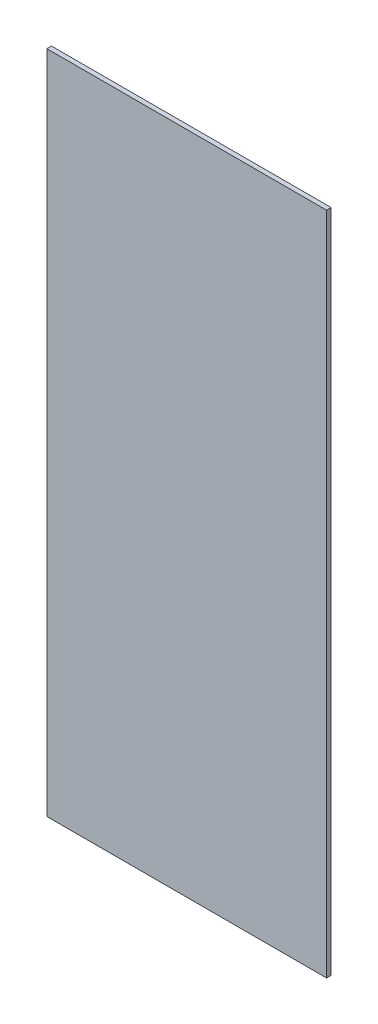
SolidWorks part; units mm, degrees
material "201 Annealed Stainless Steel (SS)"
ref_plane "Front Plane" through (0, 0, 0) normal (0, 0, 1) x (1, 0, 0)
ref_plane "Top Plane" through (0, 0, 0) normal (0, 1, 0) x (1, 0, 0)
ref_plane "Right Plane" through (0, 0, 0) normal (1, 0, 0) x (0, 0, -1)
sketch "Sketch1" plane through (0, 0, 0) normal (0, 0, 1) x (1, 0, 0)
  line L1 (-106, -145) -> (106, -145)
  line L2 (-106, -145) -> (-106, 145)
  line L3 (-106, 145) -> (106, 145)
  line L4 (106, -145) -> (106, 145)
  line L5 (-106, -145) -> (106, 145) construction
  line L6 (-106, 145) -> (106, -145) construction
  point P0 (0, 0)
  dimension "D1" = 212
  dimension "D2" = 290
extrude "Boss-Extrude1" add sketch "Sketch1" along normal blind 2
sketch "Sketch2" plane through (0, 0, 0) normal (0, 0, -1) x (-1, 0, 0)
  line L0 (61, 145) -> (61, -145) construction
  line L1 (-61, 314.7216) -> (-204.3993, 314.7216)
  line L2 (-61, 314.7216) -> (-61, -251.9618)
  line L3 (-61, -251.9618) -> (-204.3993, -251.9618)
  line L4 (-204.3993, 314.7216) -> (-204.3993, -251.9618)
  line L6 (61, 279.3211) -> (244.4765, 279.3211)
  line L7 (61, 279.3211) -> (61, -295.1839)
  line L8 (61, -295.1839) -> (244.4765, -295.1839)
  line L9 (244.4765, 279.3211) -> (244.4765, -295.1839)
  line L10 (-61, -145) -> (-61, 145) construction
  dimension "D1" = 122
extrude "Cut-Extrude1" cut sketch "Sketch2" against normal through all
sketch "Sketch3" [suppressed] plane through (49, 0, 0) normal (1, 0, 0) x (0, 0, -1)
  circle A0 centre (-6.722, 55.3681) radius 5.3835
surface "Surface-Extrude1" [suppressed] sketch "Sketch3"
sketch "Sketch4" [suppressed] plane through (-49, 0, 0) normal (-1, 0, 0) x (0, 0, 1)
  line L1 (2, 80) -> (0, 80) construction
  line L2 (0, -80) -> (0, 80) construction
  point P0 (7.5, 76)
  dimension "D1" = 4
  dimension "D2" = 7.5
ref_axis "Axis1" [suppressed] through (-49, 76, 7.5) along (1, 0, 0)
sketch "Sketch5" [suppressed] plane through (0, 0, 0) normal (0, 0, -1) x (-1, 0, 0)
  line L0 (49, 80) -> (49, -80) construction
  line L1 (-49, 80) -> (49, 80)
  line L2 (-49, 80) -> (-49, 60.2594)
  line L3 (-49, 60.2594) -> (49, 60.2594)
  line L4 (49, 80) -> (49, 60.2594)
extrude "Cut-Extrude2" [suppressed] cut sketch "Sketch5" against normal blind 3
sketch "Sketch6" [suppressed] plane through (0, 0, 2) normal (0, 0, 1) x (1, 0, 0)
  line L0 (0, 0) -> (103.2002, 0) construction
  line L1 (-40, 80) -> (-40, 108.3319) construction
  line L2 (-40, 80) -> (-27.987, 80) construction
  line L3 (0, 0) -> (0, 138.3235) construction
  line L4 (40, 80) -> (27.987, 80) construction
  line L5 (40, 80) -> (40, 108.3319) construction
  line L6 (40, -80) -> (40, -108.3319) construction
  line L7 (40, -80) -> (27.987, -80) construction
  line L8 (-40, -80) -> (-27.987, -80) construction
  line L9 (-40, -80) -> (-40, -108.3319) construction
  circle A0 centre (-40, 80) radius 4.5
  circle A2 centre (-45.8, 85.8) radius 1.95
  circle A3 centre (-45.8, 74.2) radius 1.95
  circle A4 centre (-34.2, 74.2) radius 1.95
  circle A5 centre (-34.2, 85.8) radius 1.95
  circle A6 centre (34.2, 85.8) radius 1.95
  circle A7 centre (34.2, 74.2) radius 1.95
  circle A8 centre (45.8, 74.2) radius 1.95
  circle A9 centre (45.8, 85.8) radius 1.95
  circle A10 centre (40, 80) radius 4.5
  circle A11 centre (40, -80) radius 4.5
  circle A12 centre (45.8, -85.8) radius 1.95
  circle A13 centre (45.8, -74.2) radius 1.95
  circle A14 centre (34.2, -74.2) radius 1.95
  circle A15 centre (34.2, -85.8) radius 1.95
  circle A16 centre (-34.2, -85.8) radius 1.95
  circle A17 centre (-34.2, -74.2) radius 1.95
  circle A18 centre (-45.8, -74.2) radius 1.95
  circle A19 centre (-45.8, -85.8) radius 1.95
  circle A20 centre (-40, -80) radius 4.5
  circle A21 centre (-40, 80) radius 5.1 construction
  dimension "D1" = 9
  dimension "D3" = 3.9
extrude "Leandut_holes" [suppressed] cut sketch "Sketch6" against normal through all
chamfer "Chamfer1" [suppressed] distance 5 angle 45
